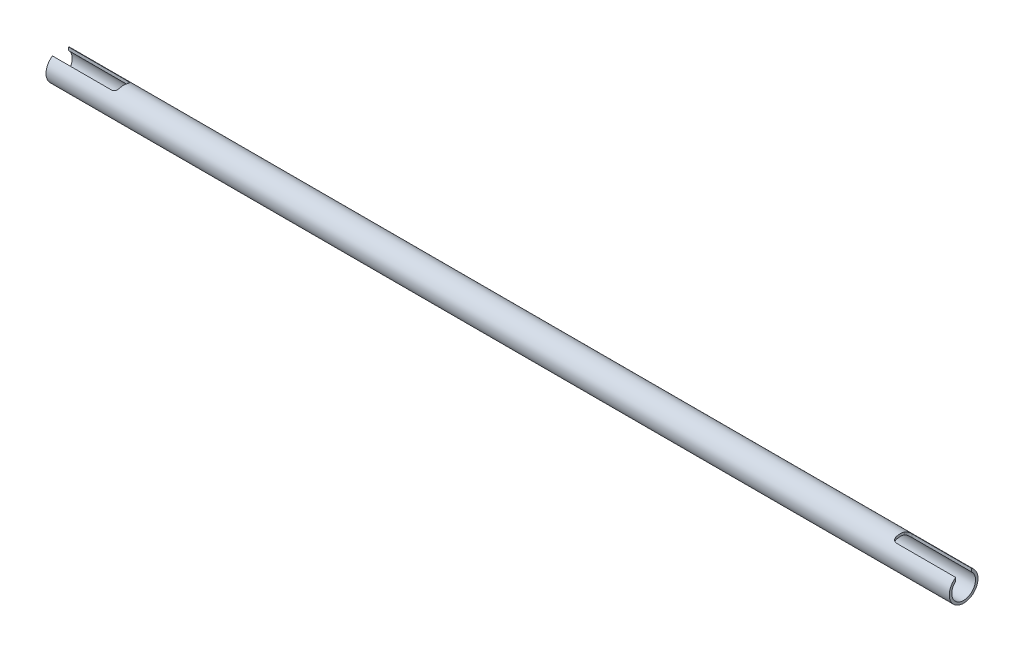
SolidWorks part; units mm, degrees
material "Acrylic (Medium-high impact)"
ref_plane "Front Plane" through (0, 0, 0) normal (0, 0, 1) x (1, 0, 0)
ref_plane "Top Plane" through (0, 0, 0) normal (0, 1, 0) x (1, 0, 0)
ref_plane "Right Plane" through (0, 0, 0) normal (1, 0, 0) x (0, 0, -1)
ref_axis "Axis1" through (0, -55, 0) along (0, 1, 0)
sketch "Sketch1" plane through (0, 0, 0) normal (1, 0, 0) x (0, 0, -1)
  circle A0 centre (0, 0) radius 9.525
  dimension "D1" = 19.05
extrude "Extrude-Thin1" add sketch "Sketch1" along normal mid plane 725 thin thin type one direction wall 2
sketch "Sketch2" plane through (0, 0, 0) normal (0, 1, 0) x (1, 0, 0)
  line L0 (362.5, -11.525) -> (362.5, 11.525) construction
  line L1 (362.5, -11.525) -> (362.5, 11.525) construction
  line L2 (314.7, -6.35) -> (362.5, -6.35)
  line L3 (311.7, -3.35) -> (311.7, 3.35)
  line L4 (362.5, -6.35) -> (362.5, 6.35)
  line L5 (314.7, 6.35) -> (362.5, 6.35)
  line L6 (311.7, -6.35) -> (362.5, 6.35) construction
  line L7 (362.5, -6.35) -> (311.7, 6.35) construction
  arc A0 (311.7, -3.35) -> (314.7, -6.35) centre (314.7, -3.35) ccw
  arc A1 (311.7, 3.35) -> (314.7, 6.35) centre (314.7, 3.35) cw
  point P2 (362.5, 0)
  point P3 (337.1, 0)
  point P4 (362.5, 0)
  dimension "D3" = 3
  dimension "D1" = 12.7
  dimension "D2" = 50.8
extrude "Cut-Extrude1" cut sketch "Sketch2" along normal blind 23
mirror "Mirror1" about plane through (0, 0, 0) normal (1, 0, 0) of "Cut-Extrude1"
